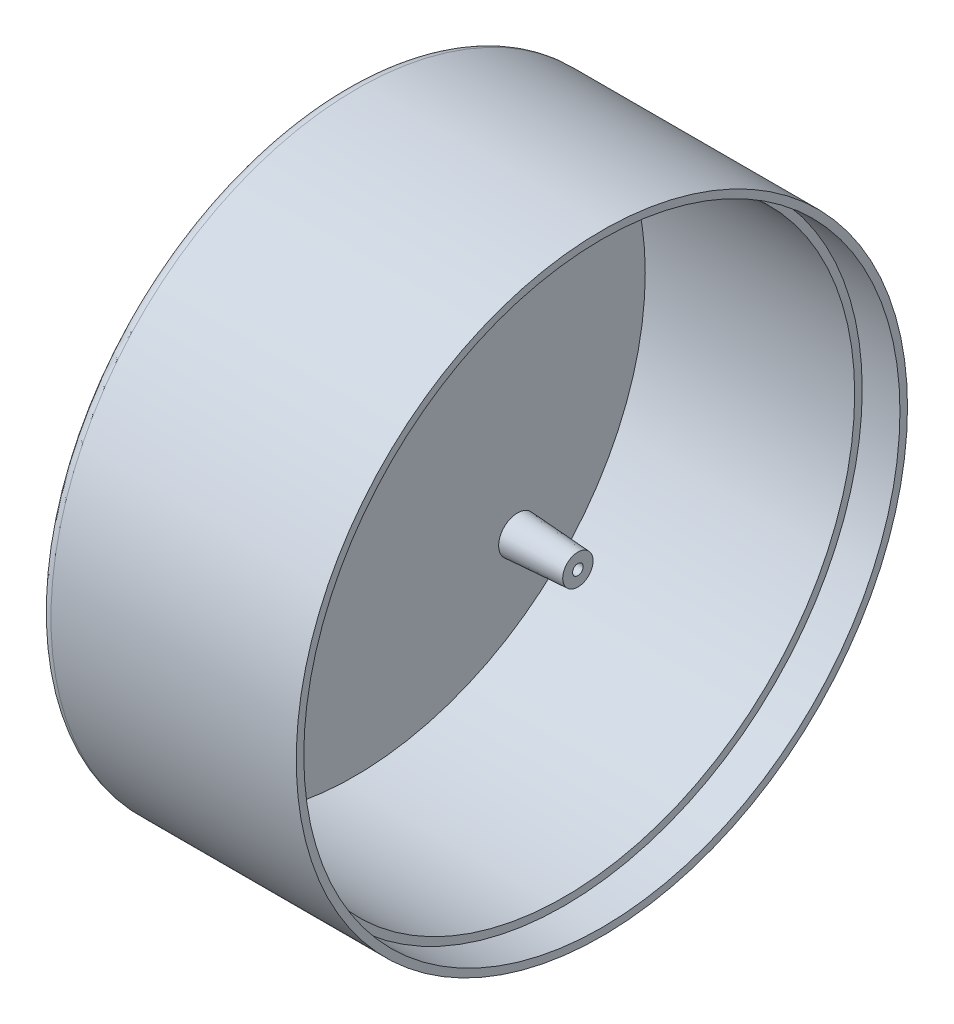
SolidWorks part; units mm, degrees
ref_plane "Front Plane" through (0, 0, 0) normal (0, 0, 1) x (1, 0, 0)
ref_plane "Top Plane" through (0, 0, 0) normal (0, 1, 0) x (1, 0, 0)
ref_plane "Right Plane" through (0, 0, 0) normal (1, 0, 0) x (0, 0, -1)
sketch "Sketch1" plane through (0, 0, 0) normal (1, 0, 0) x (0, 0, -1)
  circle A0 centre (0, 0) radius 81
  dimension "D1" = 162
extrude "Boss-Extrude1" add sketch "Sketch1" along normal blind 2.5
sketch "Sketch2" plane through (2.5, 0, 0) normal (1, 0, 0) x (0, 0, -1)
  circle A0 centre (0, 0) radius 77
  circle A1 centre (0, 0) radius 81
  dimension "D1" = 154
  dimension "D2" = 162
extrude "Boss-Extrude2" add sketch "Sketch2" along normal blind 65.5
sketch "Sketch4" plane through (2.5, 0, 0) normal (1, 0, 0) x (0, 0, -1)
  line L0 (0, 78.6345) -> (0, -85.661) construction
  line L1 (-89.8975, 0) -> (85.1443, 0) construction
  circle A0 centre (43.14, 43.135) radius 5
  circle A1 centre (-43.14, 43.135) radius 5
  circle A2 centre (43.14, -43.135) radius 5
  circle A3 centre (-43.14, -43.135) radius 5
  dimension "D1" = 10
  dimension "D2" = 43.135
  dimension "D3" = 43.14
extrude "Boss-Extrude3" add sketch "Sketch4" along normal blind 16 draft 3.5
sketch "Sketch6" plane through (18.5, 0, 0) normal (1, 0, 0) x (0, 0, -1)
  line L0 (0, 86.8722) -> (0, -106.1072) construction
  line L1 (-114.3875, 0) -> (111.4469, 0) construction
  circle A0 centre (-43.14, 43.135) radius 1.4
  circle A1 centre (43.14, 43.135) radius 1.4
  circle A2 centre (-43.14, -43.135) radius 1.4
  circle A3 centre (43.14, -43.135) radius 1.4
  dimension "D1" = 2.8
extrude "Cut-Extrude2" cut sketch "Sketch6" against normal blind 7
sketch "Sketch7" plane through (68, 0, 0) normal (1, 0, 0) x (0, 0, -1)
  circle A0 centre (0, 0) radius 79
  dimension "D1" = 158
extrude "Cut-Extrude3" cut sketch "Sketch7" against normal blind 10
fillet "Fillet1" radius 3 1 edges at (0, 0, -81)
